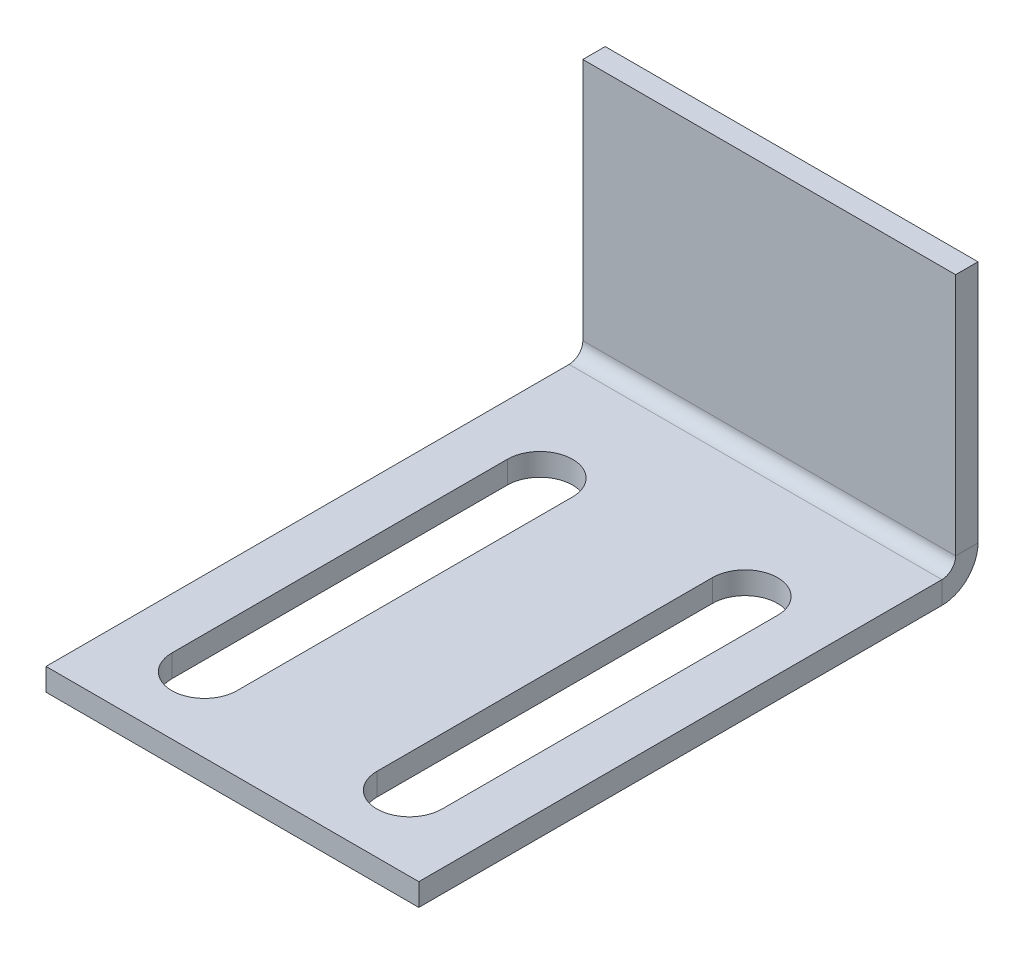
SolidWorks part; units mm, degrees
note: The reader was unsure of these and kept them because the rebuilt part matched: flange length of "Ребро-кромка1".
ref_plane "Спереди" through (0, 0, 0) normal (0, 0, 1) x (1, 0, 0)
ref_plane "Сверху" through (0, 0, 0) normal (0, 1, 0) x (1, 0, 0)
ref_plane "Справа" through (0, 0, 0) normal (1, 0, 0) x (0, 0, -1)
sketch "Эскиз1" plane through (0, 0, 0) normal (0, 0, 1) x (1, 0, 0)
  line L1 (0, 0) -> (20, 0)
  line L2 (0, 0) -> (0, 15)
  line L3 (0, 15) -> (20, 15)
  line L4 (20, 0) -> (20, 15)
  dimension "D1" = 15
  dimension "D2" = 20
base flange "Базовая кромка1" sketch "Эскиз1" thickness 1.2 reverse thickness direction no parameters "D1"=0.7366
edge flange "Ребро-кромка1" sketch "Эскиз8" flange angle 90 flange length 30 flange position material inside bend radius 0.7366 thickness 1.2 relief rectangular parameters "D6"=10
sketch "Эскиз8" plane through (0, 0, 0) normal (0, -1, 0) x (1, 0, 0)
  line L0 (0, 0) -> (20, 0) construction
  line L1 (0, 0) -> (20, 0)
  line L2 (0, 0) -> (0, 28.8)
  line L3 (0, 28.8) -> (20, 28.8)
  line L4 (20, 28.8) -> (20, 0)
bend "EdgeBend1" bend radius 0.7366 bend angle 90 parameters "D5"=1
sketch "Эскиз9" plane through (0, 1.2, 0) normal (0, 1, 0) x (1, 0, 0)
  line L0 (4.5, -6.8) -> (4.5, -24.8) construction
  line L1 (6.25, -6.8) -> (6.25, -24.8)
  line L2 (2.75, -6.8) -> (2.75, -24.8)
  line L3 (15.5, -6.8) -> (15.5, -24.8) construction
  line L4 (17.25, -6.8) -> (17.25, -24.8)
  line L5 (13.75, -6.8) -> (13.75, -24.8)
  line L6 (4.5, -24.8) -> (15.5, -24.8) construction
  line L8 (20, -28.8) -> (0, -28.8) construction
  line L9 (10, -28.8) -> (10, -24.8) construction
  arc A0 (6.25, -6.8) -> (2.75, -6.8) centre (4.5, -6.8) ccw
  arc A1 (2.75, -24.8) -> (6.25, -24.8) centre (4.5, -24.8) ccw
  arc A2 (17.25, -6.8) -> (13.75, -6.8) centre (15.5, -6.8) ccw
  arc A3 (13.75, -24.8) -> (17.25, -24.8) centre (15.5, -24.8) ccw
  point P2 (4.5, -15.8)
  point P7 (15.5, -15.8)
  dimension "D2" = 1.75
  dimension "D1" = 4
  dimension "D3" = 11
  dimension "D4" = 18
extrude "Вырез-Вытянуть1" cut sketch "Эскиз9" against normal up to next normal cut yes
sketch "Сгиб-Линии1" plane through (0, 0, 0) normal (0, 1, 0) x (1, 0, 0)
sketch "Граничная рамка1" plane through (0, 0, 0) normal (0, 1, 0) x (1, 0, 0)
sheet metal parameters "Листовой металл3" thickness 1.2 parameters "D1"=0.7366
flat pattern "Развертка3" [suppressed]
sketch "Сгиб-Линии2" plane through (0, 0, 0) normal (0, 1, 0) x (1, 0, 0)
sketch "Граничная рамка2" [suppressed] plane through (0, 0, 0) normal (0, 1, 0) x (1, 0, 0)
sheet metal parameters "Листовой металл4" thickness 1.2 parameters "D1"=0.7366
flat pattern "Развертка3" [suppressed]
sketch "Сгиб-Линии2" plane through (0, 0, 0) normal (0, 1, 0) x (1, 0, 0)
sketch "Граничная рамка2" [suppressed] plane through (0, 0, 0) normal (0, 1, 0) x (1, 0, 0)
bend of the flat pattern "Плоское состояние-<EdgeBend1>1"
sheet metal parameters "Листовой металл5" thickness 1.2 parameters "D1"=0.7366
flat pattern "Развертка3" [suppressed]
sketch "Сгиб-Линии2" plane through (0, 0, 0) normal (0, 1, 0) x (1, 0, 0)
sketch "Граничная рамка2" [suppressed] plane through (0, 0, 0) normal (0, 1, 0) x (1, 0, 0)
bend of the flat pattern "Плоское состояние-<EdgeBend1>1"
